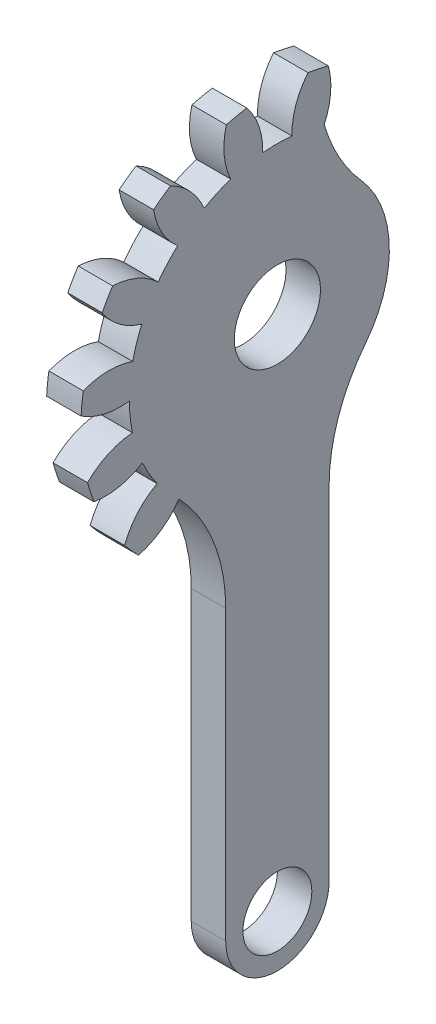
SolidWorks part; units mm, degrees
ref_plane "Front Plane" through (0, 0, 0) normal (0, 0, 1) x (1, 0, 0)
ref_plane "Top Plane" through (0, 0, 0) normal (0, 1, 0) x (1, 0, 0)
ref_plane "Right Plane" through (0, 0, 0) normal (1, 0, 0) x (0, 0, -1)
ref_plane "Plane1" through (-1.3549, 0, 0) normal (1, 0, 0) x (0, 0, -1)
sketch "Sketch1" plane through (-1.3549, 0, 0) normal (1, 0, 0) x (0, 0, -1)
  circle A0 centre (0, 0) radius 1.5
  arc A1 (-11.6614, 0.7808) -> (-8.5926, -0.0513) centre (-9.1308, 4.0384) ccw
  arc A2 (-8.5926, -0.0513) -> (-8.4155, -1.7363) centre (0, 0) ccw
  arc A3 (-8.4155, -1.7363) -> (-11.2442, -3.1883) centre (-8.0917, -5.8486) ccw
  arc A4 (-11.2442, -3.1883) -> (-10.9708, -4.0298) centre (0, 0) ccw
  arc A5 (-10.9708, -4.0298) -> (-7.8289, -3.5418) centre (-9.984, -0.0246) ccw
  arc A6 (-7.8289, -3.5418) -> (-6.9817, -5.0091) centre (0, 0) ccw
  arc A7 (-6.9817, -5.0091) -> (-8.9753, -7.4861) centre (-5.0133, -8.6341) ccw
  arc A8 (-8.9753, -7.4861) -> (-8.3833, -8.1436) centre (0, 0) ccw
  arc A9 (-8.3833, -8.1436) -> (-5.7114, -6.4199) centre (-9.1108, -4.0833) ccw
  arc A10 (-5.7114, -6.4199) -> (-4.3407, -7.4157) centre (0, 0) ccw
  arc A11 (-4.3407, -7.4157) -> (-5.1545, -10.4895) centre (-1.068, -9.9267) ccw
  arc A12 (-5.1545, -10.4895) -> (-4.3462, -10.8493) centre (0, 0) ccw
  arc A13 (-4.3462, -10.8493) -> (-2.6064, -8.1879) centre (-6.6623, -7.436) ccw
  arc A14 (-2.6064, -8.1879) -> (-0.9492, -8.5402) centre (0, 0) ccw
  arc A15 (-0.9492, -8.5402) -> (-0.4424, -11.6791) centre (3.0619, -9.5029) ccw
  arc A16 (-0.4424, -11.6791) -> (0.4424, -11.6791) centre (0, 0) ccw
  arc A17 (0.4424, -11.6791) -> (0.9492, -8.5402) centre (-3.0619, -9.5029) ccw
  arc A18 (0.9492, -8.5402) -> (2.6064, -8.1879) centre (0, 0) ccw
  arc A19 (2.6064, -8.1879) -> (4.3462, -10.8493) centre (6.6623, -7.436) ccw
  arc A20 (4.3462, -10.8493) -> (5.1545, -10.4895) centre (0, 0) ccw
  arc A21 (5.1545, -10.4895) -> (4.3407, -7.4157) centre (1.068, -9.9267) ccw
  arc A22 (4.3407, -7.4157) -> (5.7114, -6.4199) centre (0, 0) ccw
  arc A23 (5.7114, -6.4199) -> (8.3833, -8.1436) centre (9.1108, -4.0833) ccw
  arc A24 (8.3833, -8.1436) -> (8.9753, -7.4861) centre (0, 0) ccw
  arc A25 (8.9753, -7.4861) -> (6.9817, -5.0091) centre (5.0133, -8.6341) ccw
  arc A26 (6.9817, -5.0091) -> (7.8289, -3.5418) centre (0, 0) ccw
  arc A27 (7.8289, -3.5418) -> (10.9708, -4.0298) centre (9.984, -0.0246) ccw
  arc A28 (10.9708, -4.0298) -> (11.2442, -3.1883) centre (0, 0) ccw
  arc A29 (11.2442, -3.1883) -> (8.4155, -1.7363) centre (8.0917, -5.8486) ccw
  arc A30 (8.4155, -1.7363) -> (8.5926, -0.0513) centre (0, 0) ccw
  arc A31 (8.5926, -0.0513) -> (11.6614, 0.7808) centre (9.1308, 4.0384) ccw
  arc A32 (11.6614, 0.7808) -> (11.5689, 1.6608) centre (0, 0) ccw
  arc A33 (11.5689, 1.6608) -> (8.3942, 1.8367) centre (9.7709, -2.0518) ccw
  arc A34 (8.3942, 1.8367) -> (7.8706, 3.448) centre (0, 0) ccw
  arc A35 (7.8706, 3.448) -> (10.3356, 5.4564) centre (6.6989, 7.4031) ccw
  arc A36 (10.3356, 5.4564) -> (9.8932, 6.2227) centre (0, 0) ccw
  arc A37 (9.8932, 6.2227) -> (6.9214, 5.0921) centre (9.7607, 2.0998) ccw
  arc A38 (6.9214, 5.0921) -> (5.7877, 6.3512) centre (0, 0) ccw
  arc A39 (5.7877, 6.3512) -> (7.2227, 9.1886) centre (3.1086, 9.4877) ccw
  arc A40 (7.2227, 9.1886) -> (6.5069, 9.7086) centre (0, 0) ccw
  arc A41 (6.5069, 9.7086) -> (4.2519, 7.4671) centre (8.0628, 5.8883) ccw
  arc A42 (4.2519, 7.4671) -> (2.7041, 8.1562) centre (0, 0) ccw
  arc A43 (2.7041, 8.1562) -> (2.861, 11.3319) centre (-1.0192, 9.9319) ccw
  arc A44 (2.861, 11.3319) -> (1.9955, 11.5159) centre (0, 0) ccw
  arc A45 (1.9955, 11.5159) -> (0.8471, 8.5509) centre (4.9707, 8.6587) ccw
  arc A46 (0.8471, 8.5509) -> (-0.8471, 8.5509) centre (0, 0) ccw
  arc A47 (-0.8471, 8.5509) -> (-1.9955, 11.5159) centre (-4.9707, 8.6587) ccw
  arc A48 (-1.9955, 11.5159) -> (-2.861, 11.3319) centre (0, 0) ccw
  arc A49 (-2.861, 11.3319) -> (-2.7041, 8.1562) centre (1.0192, 9.9319) ccw
  arc A50 (-2.7041, 8.1562) -> (-4.2519, 7.4671) centre (0, 0) ccw
  arc A51 (-4.2519, 7.4671) -> (-6.5069, 9.7086) centre (-8.0628, 5.8883) ccw
  arc A52 (-6.5069, 9.7086) -> (-7.2227, 9.1886) centre (0, 0) ccw
  arc A53 (-7.2227, 9.1886) -> (-5.7877, 6.3512) centre (-3.1086, 9.4877) ccw
  arc A54 (-5.7877, 6.3512) -> (-6.9214, 5.0921) centre (0, 0) ccw
  arc A55 (-6.9214, 5.0921) -> (-9.8932, 6.2227) centre (-9.7607, 2.0998) ccw
  arc A56 (-9.8932, 6.2227) -> (-10.3356, 5.4564) centre (0, 0) ccw
  arc A57 (-10.3356, 5.4564) -> (-7.8706, 3.448) centre (-6.6989, 7.4031) ccw
  arc A58 (-7.8706, 3.448) -> (-8.3942, 1.8367) centre (0, 0) ccw
  arc A59 (-8.3942, 1.8367) -> (-11.5689, 1.6608) centre (-9.7709, -2.0518) ccw
  arc A60 (-11.5689, 1.6608) -> (-11.6614, 0.7808) centre (0, 0) ccw
extrude "Boss-Extrude1" add sketch "Sketch1" against normal blind 2
sketch "Sketch3" plane through (-1.3549, 0, 0) normal (1, 0, 0) x (0, 0, -1)
  line L0 (30.2794, 0) -> (-60.3175, 0) construction
  circle A0 centre (0, 0) radius 11.4072
  circle A1 centre (-20, 0) radius 11.4072 construction
  arc A2 (-8.5926, -0.0513) -> (-8.4155, -1.7363) centre (0, 0) ccw construction
  dimension "D1" = 20
extrude "Cut-Extrude1" cut sketch "Sketch3" against normal through all flip side to cut
sketch "Sketch4" plane through (-3.3549, 0, 0) normal (-1, 0, 0) x (0, 0, 1)
  circle A0 centre (0, 0) radius 2.5
  dimension "D1" = 5
extrude "Cut-Extrude2" cut sketch "Sketch4" against normal through all
sketch "Sketch5" plane through (-1.3549, 0, 0) normal (1, 0, 0) x (0, 0, -1)
  line L0 (0, 21.2664) -> (0, -72.6155) construction
  line L1 (-25.3602, -30) -> (42.7263, -30) construction
  line L2 (-3, -30) -> (-3, -2.9582)
  line L3 (3, -2.9582) -> (3, -30)
  line L4 (-3, -2.9582) -> (3, -2.9582)
  arc A0 (-3, -30) -> (3, -30) centre (0, -30) ccw
  circle A1 centre (0, -30) radius 2
  dimension "D3" = 4
  dimension "D1" = 30
  dimension "D2" = 6
extrude "Boss-Extrude2" add sketch "Sketch5" against normal blind 2
sketch "Sketch6" plane through (-1.3549, 0, 0) normal (1, 0, 0) x (0, 0, -1)
  line L0 (3, -30) -> (3, -9.3341) construction
  line L1 (3, -11.0057) -> (3, -5.7663)
  line L2 (2.0673, 6.1625) -> (3.628, 10.815)
  arc A0 (3, -5.7663) -> (2.0673, 6.1625) centre (0, 0) ccw
  arc A1 (3, -11.0057) -> (3.628, 10.815) centre (0, 0) ccw
  arc A2 (2.7041, 8.1562) -> (2.9607, 11.0163) centre (-1.0192, 9.9319) ccw construction
  dimension "D1" = 13
extrude "Cut-Extrude3" cut sketch "Sketch6" against normal through all
sketch "Sketch7" plane through (-1.3549, 0, 0) normal (1, 0, 0) x (0, 0, -1)
  line L0 (-3, -11.0057) -> (-3, -8.052)
  line L1 (-3, -9.3341) -> (-3, -30) construction
  line L2 (-4.8046, -7.124) -> (-6.3783, -9.4574)
  arc A0 (-6.3783, -9.4574) -> (-3, -11.0057) centre (0, 0) ccw
  arc A1 (-4.8046, -7.124) -> (-3, -8.052) centre (0, 0) ccw
extrude "Cut-Extrude4" cut sketch "Sketch7" against normal through all
fillet "Fillet1" radius 10 3 edges at (-2.3549, -8.052, 3) (-2.3549, 6.1625, -2.0673) (-2.3549, -5.7663, -3)
